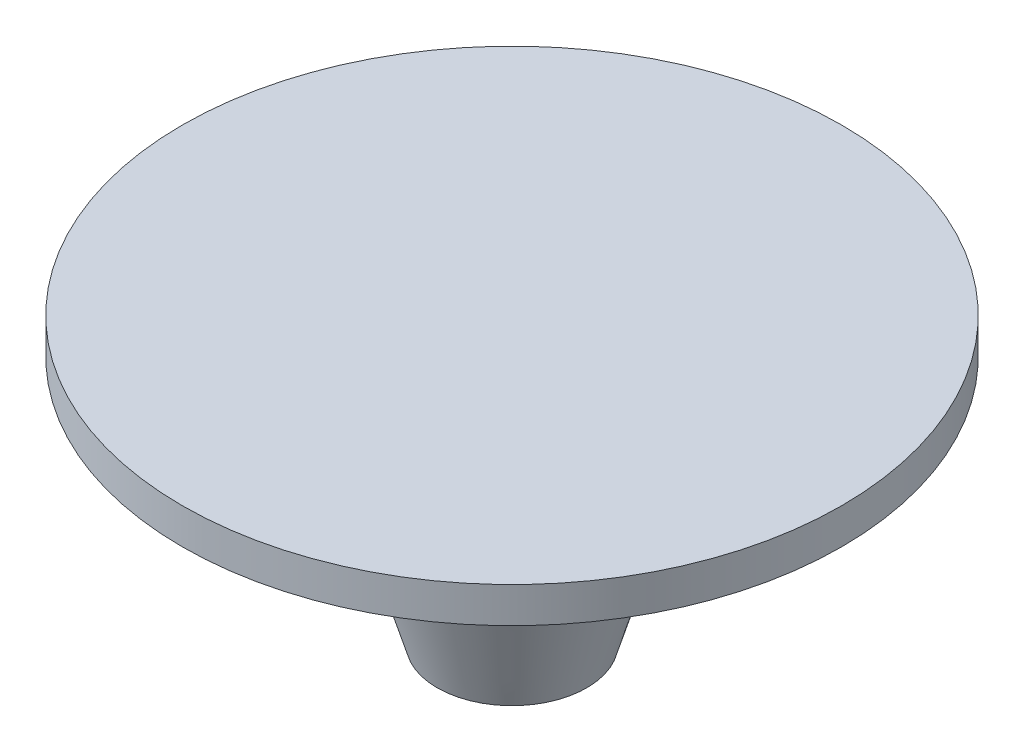
SolidWorks part; units mm, degrees
ref_plane "Front Plane" through (0, 0, 0) normal (0, 0, 1) x (1, 0, 0)
ref_plane "Top Plane" through (0, 0, 0) normal (0, 1, 0) x (1, 0, 0)
ref_plane "Right Plane" through (0, 0, 0) normal (1, 0, 0) x (0, 0, -1)
ref_axis "Axis1" through (0, 5.715, 0) along (0, -1, 0)
sketch "Sketch1" plane through (0, 0, 0) normal (0, 0, 1) x (1, 0, 0)
  line L0 (0, 299.5448) -> (0, -168.0779) construction
  line L1 (0, 0) -> (-9.25, 0)
  line L2 (-9.25, 0) -> (-9.25, -1)
  line L3 (-9.25, -1) -> (-2.1, -1)
  line L4 (-2.1, -1) -> (-2.1, -5)
  line L5 (-2.1, -5) -> (-3, -5)
  line L6 (-3, -5) -> (-2.1, -8)
  line L7 (-2.1, -8) -> (0, -8)
  line L8 (0, -8) -> (0, 0)
  dimension "D1" = 18.5
  dimension "D2" = 1
  dimension "D3" = 4
  dimension "D4" = 6
  dimension "D5" = 4.2
  dimension "D6" = 4.2
  dimension "D7" = 3
revolve "Revolve1" add sketch "Sketch1" angle 360 about L0
fillet "Fillet1" radius 0.4 2 edges at (0, -5, 2.1) (0, -1, 2.1)
